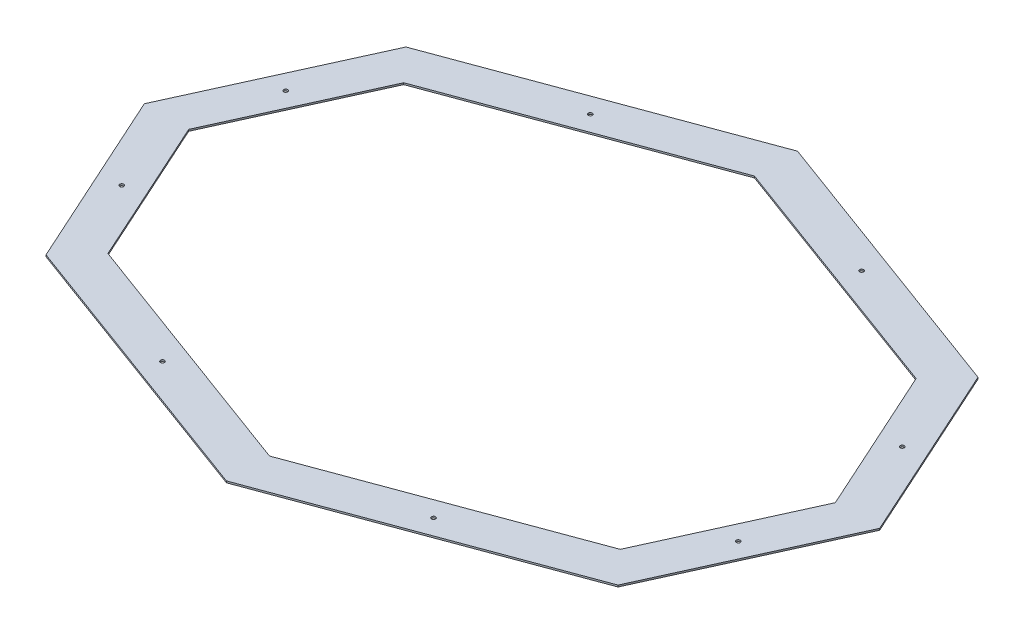
SolidWorks part; units mm, degrees
material "Rubber"
ref_plane "Front Plane" through (0, 0, 0) normal (0, 0, 1) x (1, 0, 0)
ref_plane "Top Plane" through (0, 0, 0) normal (0, 1, 0) x (1, 0, 0)
ref_plane "Right Plane" through (0, 0, 0) normal (1, 0, 0) x (0, 0, -1)
sketch "Sketch2" plane through (0, 0, 0) normal (0, 1, 0) x (1, 0, 0)
  line L0 (0, 0) -> (0, 457.2) construction
  line L1 (-609.6, 0) -> (-483.0506, 278.8894)
  line L2 (-609.6, 0) -> (0, 0) construction
  line L3 (483.0506, -278.8894) -> (-483.0506, -278.8894) construction
  line L4 (483.0506, -278.8894) -> (483.0506, 278.8894) construction
  line L5 (483.0506, 278.8894) -> (-483.0506, 278.8894) construction
  line L6 (-483.0506, -278.8894) -> (-483.0506, 278.8894) construction
  line L7 (483.0506, -278.8894) -> (-483.0506, 278.8894) construction
  line L8 (483.0506, 278.8894) -> (-483.0506, -278.8894) construction
  line L9 (-483.0506, 278.8894) -> (0, 457.2)
  line L10 (0, 457.2) -> (483.0506, 278.8894)
  line L11 (483.0506, 278.8894) -> (609.6, 0)
  line L12 (609.6, 0) -> (483.0506, -278.8894)
  line L13 (483.0506, -278.8894) -> (0, -457.2)
  line L14 (0, -457.2) -> (-483.0506, -278.8894)
  line L15 (-609.6, 0) -> (-483.0506, -278.8894)
  line L16 (-539.2916, 339.3547) -> (0, 538.4258)
  line L17 (0, 538.4258) -> (539.2916, 339.3547)
  line L18 (539.2916, 339.3547) -> (693.2779, 0)
  line L19 (693.2779, 0) -> (539.2916, -339.3547)
  line L20 (539.2916, -339.3547) -> (0, -538.4258)
  line L21 (0, -538.4258) -> (-539.2916, -339.3547)
  line L22 (-693.2779, 0) -> (-539.2916, -339.3547)
  line L23 (-693.2779, 0) -> (-539.2916, 339.3547)
  ellipse E0 centre (0, 0) end of major axis (-609.6, 0) minor radius 457.2 construction
  dimension "D1" = 609.6
  dimension "D2" = 457.2
  dimension "D3" = 30
  dimension "D4" = 76.2
extrude "Boss-Extrude1" add sketch "Sketch2" along normal mid plane 3.175
sketch "Sketch3" plane through (0, 0, 0) normal (0, 1, 0) x (1, 0, 0)
  line L0 (-511.1711, 309.122) -> (-651.4389, 0) construction
  line L1 (-651.4389, 0) -> (-511.1711, -309.122) construction
  line L2 (-511.1711, -309.122) -> (0, -497.8129) construction
  line L3 (0, -497.8129) -> (511.1711, -309.122) construction
  line L4 (511.1711, -309.122) -> (651.4389, 0) construction
  line L5 (651.4389, 0) -> (511.1711, 309.122) construction
  line L6 (511.1711, 309.122) -> (0, 497.8129) construction
  line L7 (0, 497.8129) -> (-511.1711, 309.122) construction
  line L8 (-539.2916, 339.3547) -> (-693.2779, 0)
  line L9 (-693.2779, 0) -> (-539.2916, -339.3547)
  line L10 (-539.2916, -339.3547) -> (0, -538.4258)
  line L11 (0, -538.4258) -> (539.2916, -339.3547)
  line L12 (539.2916, -339.3547) -> (693.2779, 0)
  line L13 (693.2779, 0) -> (539.2916, 339.3547)
  line L14 (539.2916, 339.3547) -> (0, 538.4258)
  line L15 (0, 538.4258) -> (-539.2916, 339.3547)
  line L16 (-539.2916, 339.3547) -> (-693.2779, 0) construction
  line L17 (-693.2779, 0) -> (-539.2916, -339.3547) construction
  line L18 (-539.2916, -339.3547) -> (0, -538.4258) construction
  line L19 (0, -538.4258) -> (539.2916, -339.3547) construction
  line L20 (539.2916, -339.3547) -> (693.2779, 0) construction
  line L21 (693.2779, 0) -> (539.2916, 339.3547) construction
  line L22 (539.2916, 339.3547) -> (0, 538.4258) construction
  line L23 (0, 538.4258) -> (-539.2916, 339.3547) construction
  circle A0 centre (581.305, 154.561) radius 3.81
  circle A1 centre (581.305, -154.561) radius 3.81
  circle A2 centre (-581.305, -154.561) radius 3.81
  circle A3 centre (-581.305, 154.561) radius 3.81
  circle A4 centre (-255.5855, 403.4675) radius 3.81
  circle A5 centre (255.5855, 403.4675) radius 3.81
  circle A6 centre (255.5855, -403.4675) radius 3.81
  circle A7 centre (-255.5855, -403.4675) radius 3.81
  dimension "D3" = 7.62
  dimension "D1" = 0
  dimension "D2" = 38.1
extrude "Cut-Extrude1" cut sketch "Sketch3" against normal through all both and the other way through all
